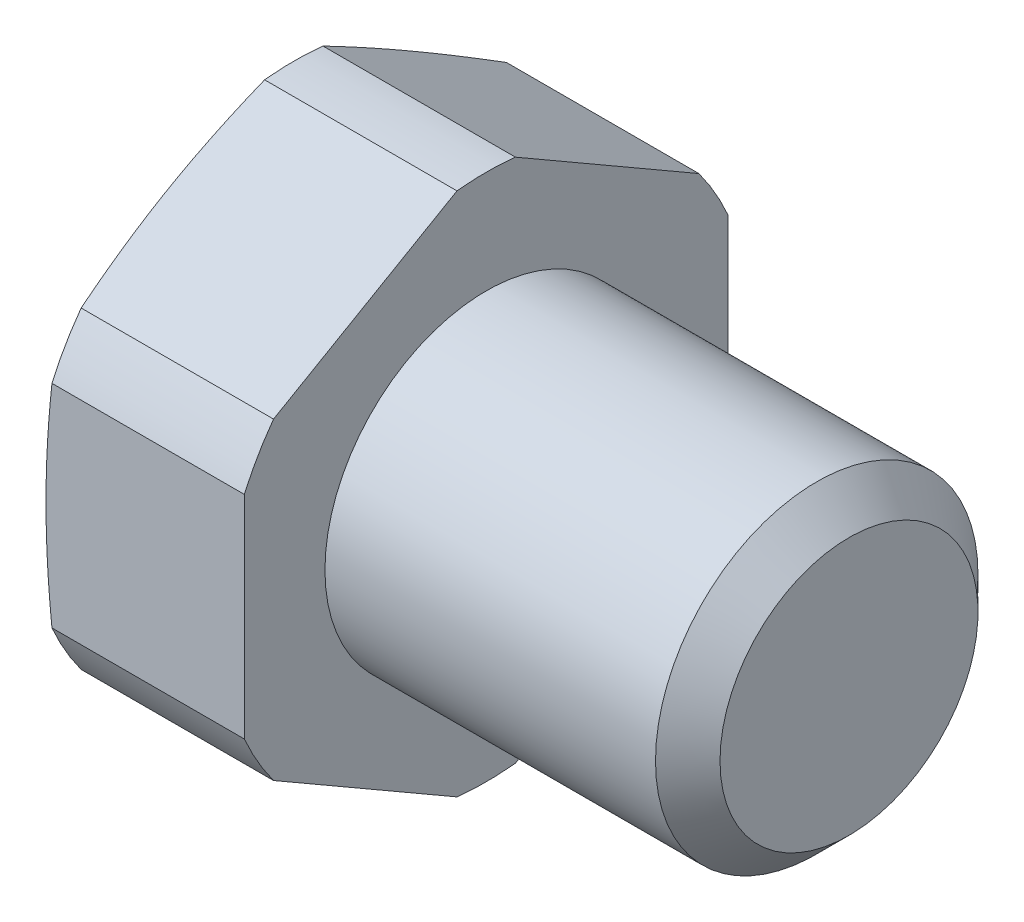
SolidWorks part; units mm, degrees
material "AISI 1020"
ref_plane "Спереди" through (0, 0, 0) normal (0, 0, 1) x (1, 0, 0)
ref_plane "Сверху" through (0, 0, 0) normal (0, 1, 0) x (1, 0, 0)
ref_plane "Справа" through (0, 0, 0) normal (1, 0, 0) x (0, 0, -1)
sketch "Эскиз1" plane through (0, 0, 0) normal (0, 0, 1) x (1, 0, 0)
  line L0 (-1000, 0) -> (49000, 0) construction
  line L1 (-10, 0) -> (-10, 11.4)
  line L2 (-10, 11.4) -> (-9.5445, 13.1)
  line L3 (-9.5445, 13.1) -> (0, 13.1)
  line L4 (0, 13.1) -> (0, 8)
  line L5 (0, 8) -> (16.4, 8)
  line L6 (18, 6.4) -> (18, 0)
  line L7 (18, 8) -> (19, 9.7321) construction
  line L8 (19, 9.7321) -> (20, 8) construction
  line L9 (20, 8) -> (18, 8) construction
  line L10 (19, 9.7321) -> (19, 8) construction
  line L11 (19, 9.7321) -> (1, 9.7321) construction
  line L12 (16.4, 8) -> (18, 6.4)
  line L13 (18, 8) -> (17.2, 7.2) construction
  line L14 (-10, 11.4) -> (-34, 11.4) construction
  line L15 (-10, 0) -> (18, 0)
  dimension "D1" = 1.6
  dimension "D2" = 15
revolve "Повернуть1" add sketch "Эскиз1" angle 360 about L0
cosmetic thread "Условное изображение резьбы1" parameters "D1"=18, "D2"=12.5359
sketch "Эскиз2" plane through (-10, 0, 0) normal (-1, 0, 0) x (0, 0, 1)
  line L1 (0, 13.8564) -> (-12, 6.9282)
  line L2 (-12, 6.9282) -> (-12, -6.9282)
  line L3 (-12, -6.9282) -> (0, -13.8564)
  line L4 (0, -13.8564) -> (12, -6.9282)
  line L5 (12, -6.9282) -> (12, 6.9282)
  line L6 (12, 6.9282) -> (0, 13.8564)
  circle A0 centre (0, 0) radius 12 construction
  dimension "D1" = 24
extrude "Вырез-Вытянуть1" cut sketch "Эскиз2" against normal up to surface (28 mm away) flip side to cut up to face at (18, 0, 6.4)
equation "\"D1@Эскиз1\"=\"_d_@Эскиз1\"/10"
equation "\"D@Эскиз1\"=\"S_@Эскиз1\"*0.95"
equation "\"D1@Эскиз2\"=\"S_@Эскиз1\""
equation "\"D1@Условное изображение резьбы1\"=\"b_@Эскиз1\""
equation "\"D2@Условное изображение резьбы1\"=\"_d_@Эскиз1\"-\"dr@Эскиз1\"*2"
